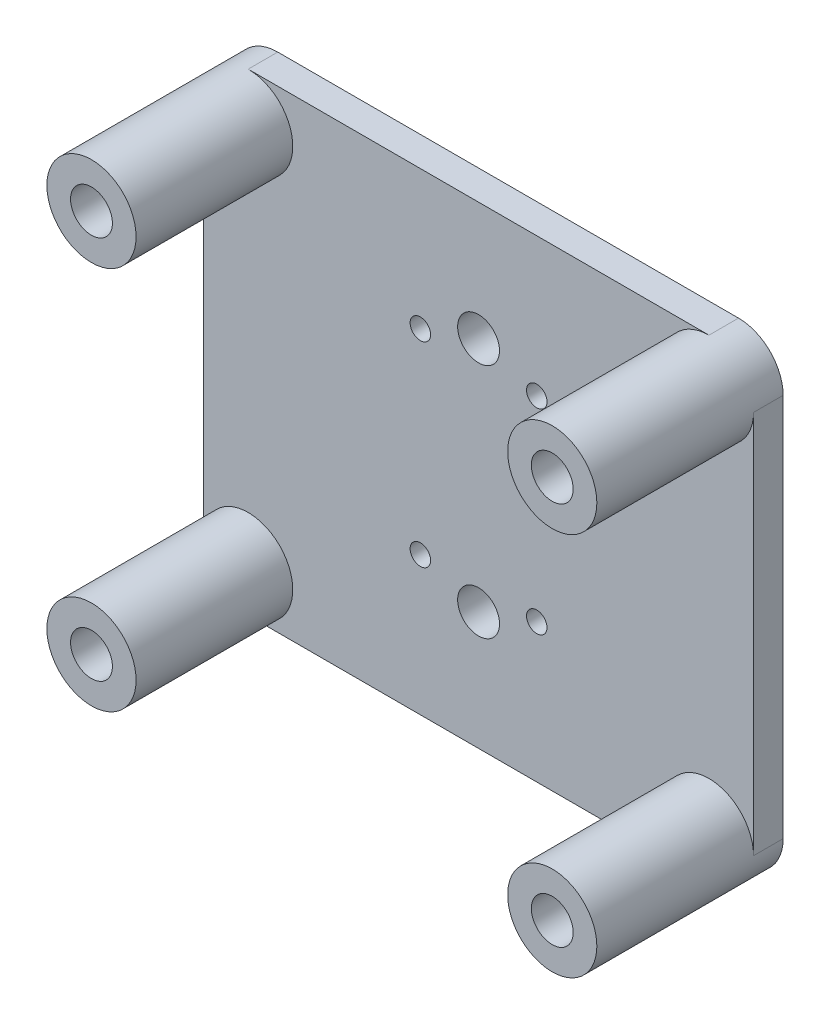
SolidWorks part; units mm, degrees
material "ABS"
ref_plane "Front Plane" through (0, 0, 0) normal (0, 0, 1) x (1, 0, 0)
ref_plane "Top Plane" through (0, 0, 0) normal (0, 1, 0) x (1, 0, 0)
ref_plane "Right Plane" through (0, 0, 0) normal (1, 0, 0) x (0, 0, -1)
sketch "Sketch1" plane through (0, 0, 0) normal (0, 0, 1) x (1, 0, 0)
  line L0 (19.1649, 16.6214) -> (6.6649, 16.6214) construction
  line L1 (6.6649, 16.6214) -> (6.6649, 37.6214) construction
  line L2 (6.6649, 37.6214) -> (19.1649, 37.6214) construction
  line L3 (19.1649, 37.6214) -> (19.1649, 16.6214) construction
  line L4 (19.1649, 27.1214) -> (6.6649, 27.1214) construction
  line L5 (12.9149, 16.6214) -> (12.9149, 37.6214) construction
  line L6 (12.9149, 14.4214) -> (12.9149, 39.8214) construction
  line L7 (-16.6126, 1.7214) -> (42.4424, 1.7214)
  line L8 (-16.6126, 1.7214) -> (-16.6126, 52.5214)
  line L9 (-16.6126, 52.5214) -> (42.4424, 52.5214)
  line L10 (42.4424, 1.7214) -> (42.4424, 52.5214)
  circle A0 centre (19.1649, 16.6214) radius 2.2
  circle A1 centre (19.1649, 16.6214) radius 1.1
  circle A2 centre (6.6649, 16.6214) radius 1.1
  circle A3 centre (6.6649, 16.6214) radius 2.2
  circle A4 centre (6.6649, 37.6214) radius 1.1
  circle A5 centre (6.6649, 37.6214) radius 2.2
  circle A6 centre (19.1649, 37.6214) radius 2.2
  circle A7 centre (19.1649, 37.6214) radius 1.1
  circle A8 centre (12.9149, 14.4214) radius 2.2479
  circle A9 centre (12.9149, 39.8214) radius 2.2479
  circle A10 centre (-11.8247, 6.5093) radius 2.2479
  circle A11 centre (-11.8247, 47.7335) radius 2.2479
  circle A12 centre (37.6545, 47.7335) radius 2.2479
  circle A13 centre (37.6545, 6.5093) radius 2.2479
  circle A14 centre (37.6545, 6.5093) radius 4.7879
  circle A15 centre (-11.8247, 6.5093) radius 4.7879
  circle A16 centre (-11.8247, 47.7335) radius 4.7879
  circle A17 centre (37.6545, 47.7335) radius 4.7879
  point P20 (-16.6126, 27.1214)
  point P21 (12.9149, 52.5214)
  point P38 (12.9149, 27.1214)
  point P39 (0, 0)
  dimension "D1" = 4.4958
  dimension "D3" = 4.4958
  dimension "D4" = 2.54
  dimension "D2" = 59.055
  dimension "D5" = 25.4
  dimension "D6" = 50.8
extrude "Boss-Extrude1" add sketch "Sketch1" along normal blind 3.175 contours A17 L9 A16 L8 A15 L7 A14 L10 A9 A8 A6 A5 A3 A0 | A17 A12 | A16 A11 | A15 A10 | A14 A13 | A0 A1 | A3 A2 | A5 A4 | A6 A7 region at (12.9149, 27.1214, 0) region at (-15.1145, 3.2195, 0) region at (34.3647, 9.7991, 0) region at (-15.1145, 51.0233, 0) region at (34.3647, 44.4437, 0) region at (17.0272, 16.6214, 0) region at (4.5272, 16.6214, 0) region at (4.5272, 37.6214, 0) region at (17.0272, 37.6214, 0)
extrude "Boss-Extrude2" add sketch "Sketch1<4>" against normal blind 5.08 contours A6 A7 | A5 A4 | A3 A2 | A0 A1 region at (17.0272, 16.6214, 0) region at (4.5272, 16.6214, 0) region at (4.5272, 37.6214, 0) region at (17.0272, 37.6214, 0)
sketch "Sketch1<4>" plane through (0, 0, 0) normal (0, 0, 1) x (1, 0, 0) same geometry as "Sketch1"
extrude "Boss-Extrude3" add sketch "Sketch1<5>" along normal blind 20.0025 contours A17 A12 | A16 A11 | A15 A10 | A14 A13 region at (-15.1145, 3.2195, 0) region at (34.3647, 9.7991, 0) region at (-15.1145, 51.0233, 0) region at (34.3647, 44.4437, 0)
sketch "Sketch1<5>" plane through (0, 0, 0) normal (0, 0, 1) x (1, 0, 0) same geometry as "Sketch1"
